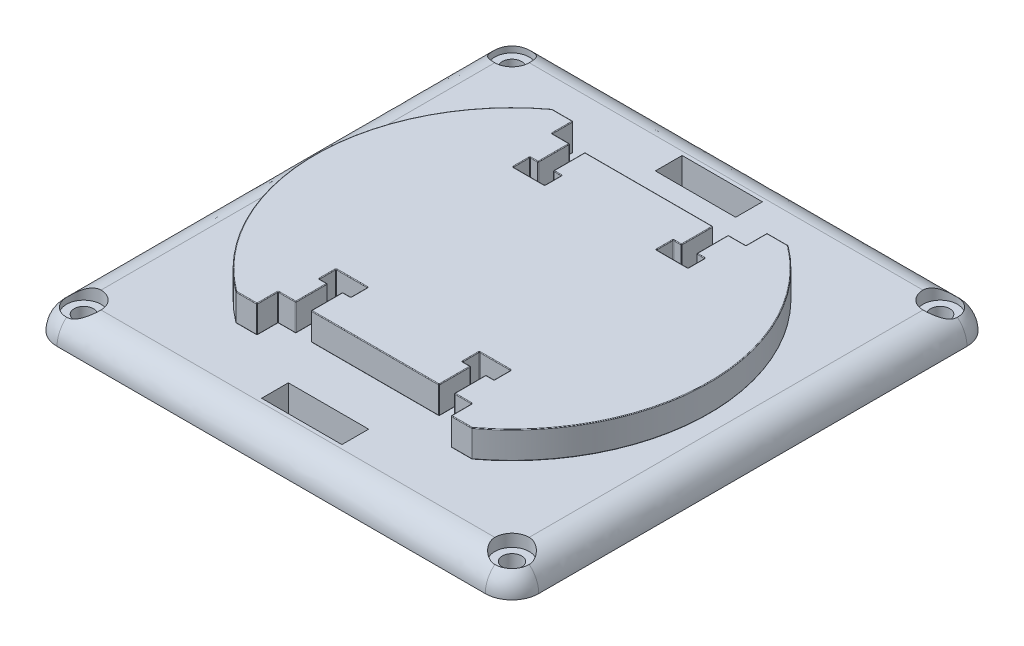
SolidWorks part; units mm, degrees
ref_plane "Front Plane" through (0, 0, 0) normal (0, 0, 1) x (1, 0, 0)
ref_plane "Top Plane" through (0, 0, 0) normal (0, 1, 0) x (1, 0, 0)
ref_plane "Right Plane" through (0, 0, 0) normal (1, 0, 0) x (0, 0, -1)
sketch "Sketch1" plane through (0, 0, 0) normal (0, 1, 0) x (1, 0, 0)
  line L0 (-28, 37.5) -> (-23, 37.5)
  line L1 (23, 37.5) -> (28, 37.5)
  line L3 (-23, 37.5) -> (-23, 32.5)
  line L4 (-23, 32.5) -> (23, 32.5)
  line L5 (23, 37.5) -> (23, 32.5)
  line L6 (0, 0) -> (-46.8001, 0) construction
  line L7 (23, -37.5) -> (28, -37.5)
  line L8 (23, -37.5) -> (23, -32.5)
  line L9 (-23, -32.5) -> (23, -32.5)
  line L10 (-23, -37.5) -> (-23, -32.5)
  line L11 (-28, -37.5) -> (-23, -37.5)
  arc A0 (-28, 37.5) -> (-28, -37.5) centre (0, 0) ccw
  arc A1 (28, -37.5) -> (28, 37.5) centre (0, 0) ccw
  point P10 (0, 32.5)
  dimension "D1" = 5
  dimension "D2" = 37.5
  dimension "D3" = 46
  dimension "D4" = 5
extrude "Boss-Extrude1" add sketch "Sketch1" along normal blind 6.5
sketch "Sketch2" plane through (0, 6.5, 0) normal (0, 1, 0) x (1, 0, 0)
  line L0 (23, 32.5) -> (-23, 32.5) construction
  line L1 (-18.8, 25) -> (-15.2, 25)
  line L2 (-18.8, 25) -> (-18.8, 32.5)
  line L3 (-18.8, 32.5) -> (-15.2, 32.5)
  line L4 (-15.2, 25) -> (-15.2, 32.5)
  line L5 (-18.8, 25) -> (-15.2, 32.5) construction
  line L6 (-18.8, 32.5) -> (-15.2, 25) construction
  line L7 (-23, 32.5) -> (-23, 37.5) construction
  line L8 (-13.25, 21) -> (-20.75, 21)
  line L9 (-13.25, 21) -> (-13.25, 25)
  line L10 (-13.25, 25) -> (-20.75, 25)
  line L11 (-20.75, 21) -> (-20.75, 25)
  line L12 (-13.25, 21) -> (-20.75, 25) construction
  line L13 (-13.25, 25) -> (-20.75, 21) construction
  line L14 (0, 0) -> (-46.8001, 0) construction
  line L15 (0, 0) -> (0, 32.5) construction
  line L16 (13.25, 25) -> (20.75, 21) construction
  line L17 (13.25, 21) -> (20.75, 25) construction
  line L18 (18.8, 32.5) -> (15.2, 25) construction
  line L19 (18.8, 25) -> (15.2, 32.5) construction
  line L20 (20.75, 21) -> (20.75, 25)
  line L21 (13.25, 25) -> (20.75, 25)
  line L22 (13.25, 21) -> (13.25, 25)
  line L23 (13.25, 21) -> (20.75, 21)
  line L24 (15.2, 25) -> (15.2, 32.5)
  line L25 (18.8, 32.5) -> (15.2, 32.5)
  line L26 (18.8, 25) -> (18.8, 32.5)
  line L27 (18.8, 25) -> (15.2, 25)
  line L28 (18.8, -25) -> (15.2, -32.5) construction
  line L29 (18.8, -32.5) -> (15.2, -25) construction
  line L30 (13.25, -21) -> (20.75, -25) construction
  line L31 (13.25, -25) -> (20.75, -21) construction
  line L32 (-13.25, -25) -> (-20.75, -21) construction
  line L33 (-13.25, -21) -> (-20.75, -25) construction
  line L34 (-18.8, -32.5) -> (-15.2, -25) construction
  line L35 (-18.8, -25) -> (-15.2, -32.5) construction
  line L36 (18.8, -25) -> (15.2, -25)
  line L37 (18.8, -25) -> (18.8, -32.5)
  line L38 (18.8, -32.5) -> (15.2, -32.5)
  line L39 (15.2, -25) -> (15.2, -32.5)
  line L40 (13.25, -21) -> (20.75, -21)
  line L41 (13.25, -21) -> (13.25, -25)
  line L42 (13.25, -25) -> (20.75, -25)
  line L43 (20.75, -21) -> (20.75, -25)
  line L44 (-20.75, -21) -> (-20.75, -25)
  line L45 (-13.25, -25) -> (-20.75, -25)
  line L46 (-13.25, -21) -> (-13.25, -25)
  line L47 (-13.25, -21) -> (-20.75, -21)
  line L48 (-15.2, -25) -> (-15.2, -32.5)
  line L49 (-18.8, -32.5) -> (-15.2, -32.5)
  line L50 (-18.8, -25) -> (-18.8, -32.5)
  line L51 (-18.8, -25) -> (-15.2, -25)
  arc A0 (-28, 37.5) -> (-28, -37.5) centre (0, 0) ccw construction
  point P0 (-17, 28.75)
  point P7 (-17, 23)
  point P29 (17, 23)
  point P30 (17, 28.75)
  point P47 (17, -28.75)
  point P48 (17, -23)
  point P49 (-17, -23)
  point P50 (-17, -28.75)
  dimension "D1" = 4.2
  dimension "D2" = 3.6
  dimension "D3" = 7.5
  dimension "D4" = 4
  dimension "D5" = 7.5
extrude "Cut-Extrude1" cut sketch "Sketch2" against normal through all contours L4 L3 L2 L1 | L9 L10 L11 L8 | L26 L25 L24 L27 | L20 L21 L22 L23 | L43 L42 L41 L40 | L37 L38 L39 L36 | L48 L49 L50 L51 | L46 L45 L44 L47
fillet "Fillet1" radius 0.15 132 edges at (-18.8, 3.25, -32.5) (-18.8, 6.5, -28.75) (-20.9, 6.5, -32.5) (-18.8, 0, -28.75) (-18.8, 3.25, -25) (-23, 3.25, -32.5) (-20.9, 0, -32.5) (-19.775, 6.5, -25) (-23, 6.5, -35) (-19.775, 0, -25) (-20.75, 3.25, -25) (-23, 3.25, -37.5) (-23, 0, -35) (-20.75, 6.5, -23) (-25.5, 6.5, -37.5) (-20.75, 0, -23) (-20.75, 3.25, -21) (-28, 3.25, -37.5) (-25.5, 0, -37.5) (-17, 6.5, -21) (-46.8001, 6.5, 0) (-17, 0, -21) (-13.25, 3.25, -21) (-28, 3.25, 37.5) (-46.8001, 0, 0) (-13.25, 6.5, -23) (-25.5, 6.5, 37.5) (-13.25, 0, -23) (-13.25, 3.25, -25) (-23, 3.25, 37.5) (-25.5, 0, 37.5) (-14.225, 6.5, -25) (-23, 6.5, 35) (-14.225, 0, -25) (-15.2, 3.25, -25) (-23, 3.25, 32.5) (-23, 0, 35) (-15.2, 6.5, -28.75) (-20.9, 6.5, 32.5) (-15.2, 0, -28.75) (-15.2, 3.25, -32.5) (-20.9, 0, 32.5) (-18.8, 3.25, 32.5) (0, 6.5, -32.5) (-18.8, 6.5, 28.75) (0, 0, -32.5) (15.2, 3.25, -32.5) (-18.8, 0, 28.75) (-18.8, 3.25, 25) (15.2, 6.5, -28.75) (-19.775, 6.5, 25) (15.2, 0, -28.75) (15.2, 3.25, -25) (-20.75, 3.25, 25) (-19.775, 0, 25) (14.225, 6.5, -25) (-20.75, 6.5, 23) (14.225, 0, -25) (13.25, 3.25, -25) (-20.75, 0, 23) (-20.75, 3.25, 21) (13.25, 6.5, -23) (-17, 6.5, 21) (13.25, 0, -23) (13.25, 3.25, -21) (-17, 0, 21) (-13.25, 3.25, 21) (17, 6.5, -21) (-13.25, 6.5, 23) (17, 0, -21) (20.75, 3.25, -21) (-13.25, 0, 23) (-13.25, 3.25, 25) (20.75, 6.5, -23) (-14.225, 6.5, 25) (20.75, 0, -23) (20.75, 3.25, -25) (-14.225, 0, 25) (-15.2, 3.25, 25) (19.775, 6.5, -25) (-15.2, 6.5, 28.75) (19.775, 0, -25) (18.8, 3.25, -25) (-15.2, 3.25, 32.5) (-15.2, 0, 28.75) (18.8, 6.5, -28.75) (0, 6.5, 32.5) (18.8, 0, -28.75) (18.8, 3.25, -32.5) (0, 0, 32.5) (15.2, 3.25, 32.5) (20.9, 6.5, -32.5) (15.2, 6.5, 28.75) (20.9, 0, -32.5) (23, 3.25, -32.5) (15.2, 0, 28.75) (15.2, 3.25, 25) (23, 6.5, -35) (14.225, 6.5, 25) (23, 0, -35) (23, 3.25, -37.5) (14.225, 0, 25) (13.25, 3.25, 25) (25.5, 6.5, -37.5) (13.25, 6.5, 23) (25.5, 0, -37.5) (28, 3.25, -37.5) (13.25, 0, 23) (13.25, 3.25, 21) (46.8001, 6.5, 0) (17, 6.5, 21) (46.8001, 0, 0) (28, 3.25, 37.5) (20.75, 3.25, 21) (17, 0, 21) (25.5, 6.5, 37.5) (20.75, 6.5, 23) (23, 3.25, 37.5) (25.5, 0, 37.5) (20.75, 3.25, 25) (20.75, 0, 23) (23, 6.5, 35) (19.775, 6.5, 25) (23, 0, 35) (23, 3.25, 32.5) (18.8, 3.25, 25) (19.775, 0, 25) (20.9, 6.5, 32.5) (18.8, 6.5, 28.75) (20.9, 0, 32.5) (18.8, 0, 28.75) (18.8, 3.25, 32.5)
sketch "Sketch3" plane through (0, 0, 0) normal (0, -1, 0) x (1, 0, 0)
  line L0 (0, 0) -> (0, -57.15) construction
  line L1 (-57.15, 57.15) -> (57.15, 57.15)
  line L2 (-57.15, 57.15) -> (-57.15, -57.15)
  line L3 (-57.15, -57.15) -> (57.15, -57.15)
  line L4 (57.15, 57.15) -> (57.15, -57.15)
  line L5 (-57.15, 57.15) -> (57.15, -57.15) construction
  line L6 (-57.15, -57.15) -> (57.15, 57.15) construction
  line L8 (0, 0) -> (-57.15, 0) construction
  line L9 (0, 0) -> (0, -57.15) construction
  line L10 (0, 0) -> (-57.15, 0) construction
  point P0 (0, 0)
  point P7 (57.15, -57.15)
  point P10 (-57.15, -57.15)
  point P11 (-57.15, 57.15)
  point P12 (57.15, 57.15)
  point P13 (-57.15, 0)
  point P14 (57.15, -57.15)
  point P16 (-57.15, -57.15)
  point P17 (-57.15, 57.15)
  dimension "D1" = 114.3
  dimension "D2" = 114.3
extrude "Boss-Extrude2" add sketch "Sketch3" along normal blind 6.35
fillet "Fillet4" radius 6.35 1 edges at (57.15, 0, 0)
fillet "Fillet5" radius 6.35 2 edges
fillet "Fillet6" radius 6.35 2 edges
fillet "Fillet7" radius 6.35 3 edges
sketch "Sketch4" plane through (0, 0, 0) normal (0, -1, 0) x (-1, 0, 0)
  line L0 (0, 0) -> (0, 50.8) construction
  line L1 (-50.8, 50.8) -> (50.8, 50.8) construction
  line L2 (0, 0) -> (-50.8, 0) construction
  line L3 (-50.8, -50.8) -> (-50.8, 50.8) construction
  circle A1 centre (-50.8, 50.8) radius 4.0894
  circle A2 centre (-50.8, 50.8) radius 2.286
  circle A3 centre (50.8, 50.8) radius 2.286
  circle A4 centre (50.8, 50.8) radius 4.0894
  circle A5 centre (-50.8, -50.8) radius 2.286
  circle A6 centre (-50.8, -50.8) radius 4.0894
  circle A7 centre (50.8, -50.8) radius 2.286
  circle A8 centre (50.8, -50.8) radius 4.0894
extrude "Cut-Extrude3" cut sketch "Sketch4" along normal blind 2.921 contours A4 | A1 | A6 | A8
sketch "Sketch5" plane through (0, 0, 0) normal (0, 1, 0) x (1, 0, 0)
  line L0 (0, 0) -> (0, 50.8) construction
  line L1 (46.7106, 50.8) -> (-46.7106, 50.8) construction
  line L2 (0, 0) -> (50.8, 0) construction
  line L3 (50.8, -46.7106) -> (50.8, 46.7106) construction
  circle A0 centre (50.8, 50.8) radius 2.286
  circle A1 centre (-50.8, 50.8) radius 2.286
  circle A2 centre (50.8, -50.8) radius 2.286
  circle A3 centre (-50.8, -50.8) radius 2.286
extrude "Cut-Extrude4" cut sketch "Sketch5" against normal through all
sketch "Sketch6" plane through (0, 0, 0) normal (0, 1, 0) x (1, 0, 0)
  line L0 (0, 50.8) -> (0, -50.8) construction
  line L1 (46.7106, 50.8) -> (-46.7106, 50.8) construction
  line L2 (-46.7106, -50.8) -> (46.7106, -50.8) construction
  line L3 (-50.8, 0) -> (50.8, 0) construction
  line L4 (-50.8, 46.7106) -> (-50.8, -46.7106) construction
  line L5 (50.8, -46.7106) -> (50.8, 46.7106) construction
  line L6 (-50.8, -46.7106) -> (50.8, -46.7106) construction
  line L7 (-9.525, 49.8856) -> (-9.525, 43.5356)
  line L8 (-9.525, -49.8856) -> (9.525, -49.8856)
  line L9 (-9.525, -49.8856) -> (-9.525, -43.5356)
  line L10 (-9.525, -43.5356) -> (9.525, -43.5356)
  line L11 (9.525, -49.8856) -> (9.525, -43.5356)
  line L12 (-9.525, -49.8856) -> (9.525, -43.5356) construction
  line L13 (-9.525, -43.5356) -> (9.525, -49.8856) construction
  line L14 (-9.525, 49.8856) -> (9.525, 49.8856)
  line L15 (9.525, 49.8856) -> (9.525, 43.5356)
  line L16 (-9.525, 43.5356) -> (9.525, 43.5356)
  point P16 (0, -46.7106)
  dimension "D1" = 6.35
  dimension "D2" = 19.05
extrude "Cut-Extrude5" cut sketch "Sketch6" against normal through all
